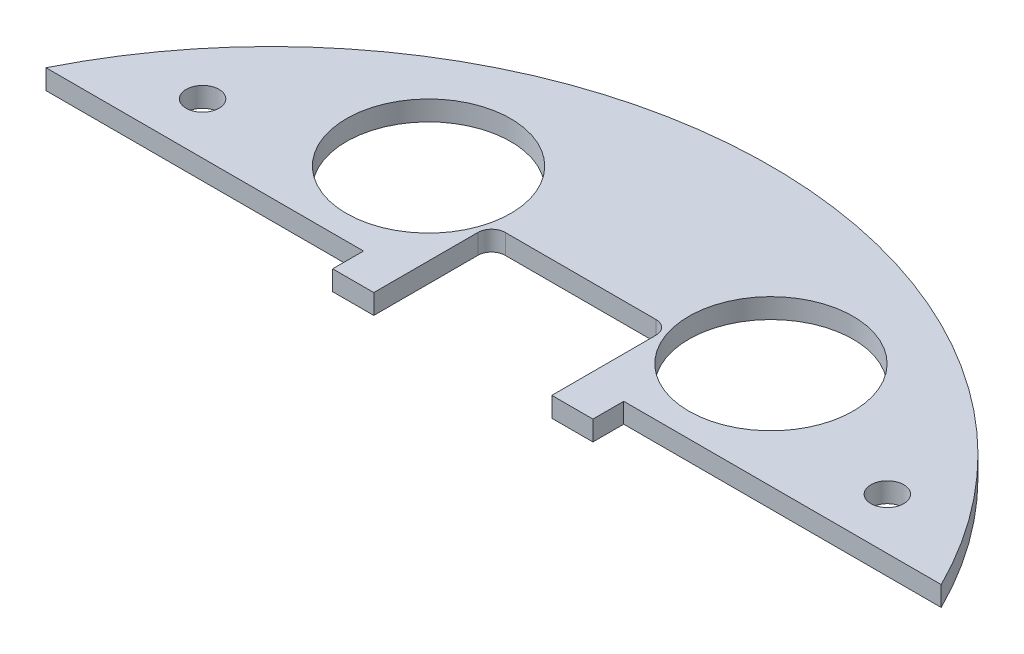
SolidWorks part; units mm, degrees
material "Acrylic (Medium-high impact)"
ref_plane "Front Plane" through (0, 0, 0) normal (0, 0, 1) x (1, 0, 0)
ref_plane "Top Plane" through (0, 0, 0) normal (0, 1, 0) x (1, 0, 0)
ref_plane "Right Plane" through (0, 0, 0) normal (1, 0, 0) x (0, 0, -1)
sketch "Sketch1" plane through (0, 0, 0) normal (0, 1, 0) x (1, 0, 0)
  line L0 (0, -85) -> (-32.7511, -65.2408) construction
  line L1 (0, -85) -> (0, 0) construction
  arc A0 (36.8566, -63.0126) -> (-36.8566, -63.0126) centre (0, 0) ccw
  arc A1 (30.3631, -61.7375) -> (-30.3631, -61.7375) centre (0, -85) ccw
  arc A2 (36.8566, -63.0126) -> (30.3631, -61.7375) centre (34.3322, -58.6967) cw
  arc A3 (-30.3631, -61.7375) -> (-36.8566, -63.0126) centre (-34.3322, -58.6967) cw
  dimension "D1" = 146
  dimension "D2" = 76.5
  dimension "D4" = 5
  dimension "D3" = 85
extrude "Boss-Extrude1" add sketch "Sketch1" along normal blind 2.9
sketch "solenoid placement" plane through (0, 2.9, 0) normal (0, 1, 0) x (1, 0, 0)
  line L4 (-19, -36) -> (19, -36)
  line L5 (-19, 28) -> (-19, -36)
  line L6 (19, 28) -> (-19, 28)
  line L7 (19, -36) -> (19, 28)
  line L8 (-19, -36) -> (19, -36)
  line L9 (-19, 28) -> (-19, -36)
  line L10 (19, 28) -> (-19, 28)
  line L11 (19, -36) -> (19, 28)
  dimension "D1" = 0
extrude "Cut-Extrude1" cut sketch "solenoid placement" against normal through all
sketch "Sketch4" plane through (0, 2.9, 0) normal (0, 1, 0) x (1, 0, 0)
  line L6 (-13, 28) -> (13, 28)
  line L7 (13, 28) -> (13, 43.2)
  line L8 (11, 45.2) -> (-11, 45.2)
  line L9 (-13, 43.2) -> (-13, 28)
  line L10 (-13, 28) -> (13, 28)
  line L11 (13, 28) -> (13, 43.2)
  line L12 (11, 45.2) -> (-11, 45.2)
  line L13 (-13, 43.2) -> (-13, 28)
  arc A4 (13, 43.2) -> (11, 45.2) centre (11, 43.2) ccw
  arc A5 (13, 43.2) -> (11, 45.2) centre (11, 43.2) ccw
  arc A6 (-11, 45.2) -> (-13, 43.2) centre (-11, 43.2) ccw
  arc A7 (-11, 45.2) -> (-13, 43.2) centre (-11, 43.2) ccw
  dimension "D1" = 0
extrude "Cut-Extrude4" cut sketch "Sketch4" against normal through all
sketch "Sketch5" plane through (0, 2.9, 0) normal (0, 1, 0) x (1, 0, 0)
  circle A1 centre (-25, 48) radius 12
  circle A2 centre (-25, 48) radius 12
  circle A3 centre (25, 48) radius 12
  circle A4 centre (25, 48) radius 12
  dimension "D1" = 0
  dimension "D2" = 0
extrude "Cut-Extrude5" cut sketch "Sketch5" against normal through all
sketch "Sketch6" plane through (0, 2.9, 0) normal (0, 1, 0) x (1, 0, 0)
  circle A1 centre (40, -40) radius 2.4
  circle A2 centre (40, -40) radius 2.4
  circle A3 centre (-40, -40) radius 2.4
  circle A4 centre (-40, -40) radius 2.4
  circle A5 centre (-50, 40) radius 2.4
  circle A6 centre (-50, 40) radius 2.4
  circle A7 centre (50, 40) radius 2.4
  circle A8 centre (50, 40) radius 2.4
  dimension "D1" = 0
  dimension "D2" = 0
  dimension "D3" = 0
  dimension "D4" = 0
extrude "Cut-Extrude6" cut sketch "Sketch6" against normal through all
sketch "Sketch3" plane through (0, 2.9, 0) normal (0, 1, 0) x (1, 0, 0)
  line L0 (-19, 28) -> (19, 28)
  line L1 (-73, -32.5) -> (73, -32.5)
  line L2 (-73, -32.5) -> (-73, 32.5)
  line L3 (-73, 32.5) -> (-19, 32.5)
  line L4 (73, -32.5) -> (73, 32.5)
  line L5 (-73, -32.5) -> (73, 32.5) construction
  line L6 (-73, 32.5) -> (73, -32.5) construction
  line L7 (19, 28) -> (19, 32.5)
  line L8 (-19, 28) -> (-19, 32.5)
  line L9 (19, 32.5) -> (73, 32.5)
  arc A0 (36.8566, -63.0126) -> (-36.8566, -63.0126) centre (0, 0) ccw construction
  point P0 (0, 0)
  dimension "D1" = 65
extrude "Cut-Extrude3" cut sketch "Sketch3" against normal through all
sketch "Sketch8" plane through (0, 2.9, 0) normal (0, 1, 0) x (1, 0, 0)
  line L4 (5, 0) -> (-5, 0)
  line L5 (5, -62.8025) -> (5, 0)
  line L6 (-5, -62.8025) -> (5, -62.8025)
  line L7 (-5, 0) -> (-5, -62.8025)
  line L8 (5, 0) -> (-5, 0)
  line L9 (5, -62.8025) -> (5, 0)
  line L10 (-5, -62.8025) -> (5, -62.8025)
  line L11 (-5, 0) -> (-5, -62.8025)
  dimension "D1" = 0
extrude "Cut-Extrude9" cut sketch "Sketch8" against normal through all and the other way through all
delete or keep bodies "Body-Delete/Keep 1" type delete bodies bodies 116 117
equation "\"smallPulleyTeeth\"= 15"
equation "\"largePulleyTeeth\"= 30"
equation "\"eighthThick\"= 2.9mm"
equation "\"sixteenthThick\" = 1.7mm"
equation "\"quarterThick\"=6.0mm"
equation "\"OD\" = 146mm"
equation "\"puckAngle\" = 60.5deg"
equation "\"D1@Sketch1\"=\"OD\""
equation "\"puckDiam\" = 76.5mm"
equation "\"D2@Sketch1\"=\"puckDiam\""
equation "\"D1@Boss-Extrude1\"=\"eighthThick\""
equation "\"axlePress\" = 5.9mm"
equation "\"press\" = 0.2mm"
equation "\"wheelClear\" = 0.3mm"
equation "\"10-32clear\" = 4.8mm"
equation "\"6-32clear\" = 3.3mm"
equation "\"8-32clear\" = 4.0mm"
equation "\"wheelHeight\" = 22mm"
equation "\"wheelWell\" = 65mm"
equation "\"D1@Sketch3\"=\"wheelWell\""
equation "\"puckDist\" = 85mm"
equation "\"scoopFillet\" = 5mm"
equation "\"4-40clear\" = 3.0mm"
equation "\"D3@Sketch1\"=\"puckDist\""
equation "\"D4@Sketch1\"=\"scoopFillet\""
